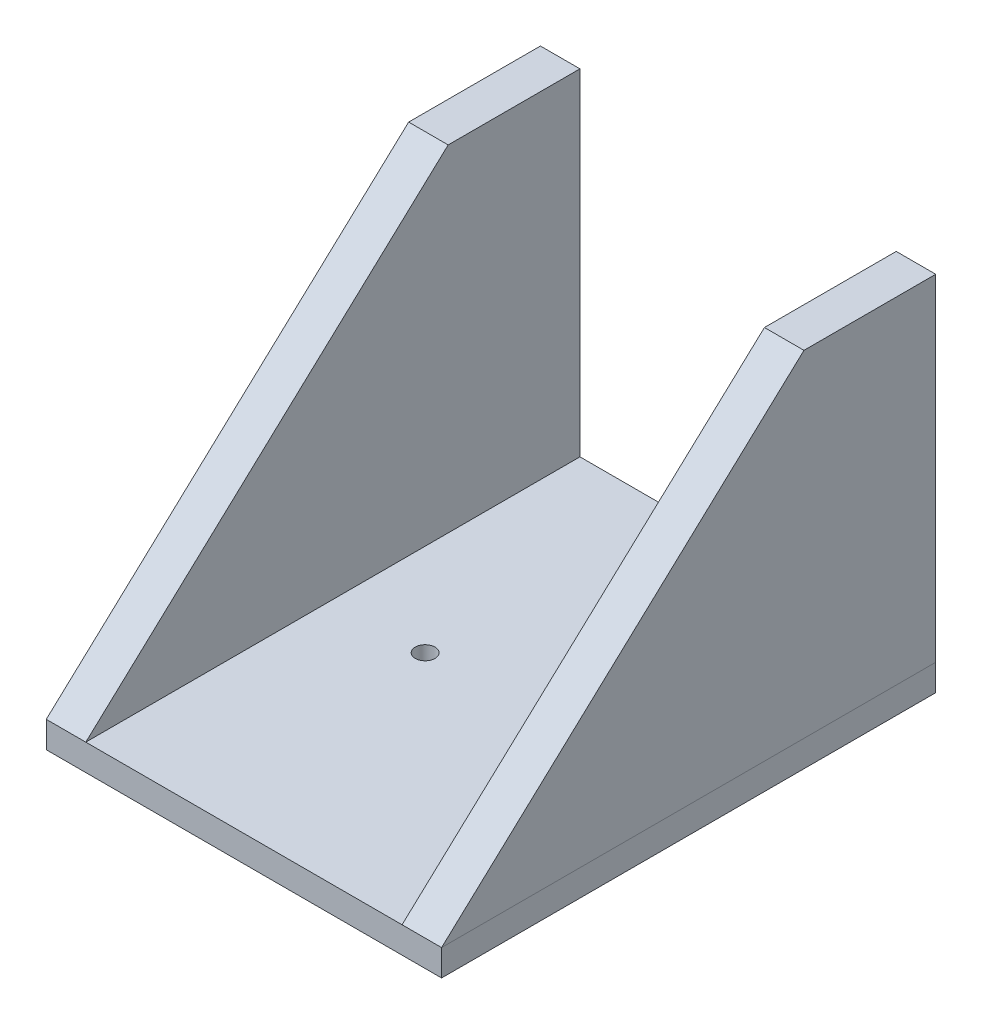
SolidWorks part; units mm, degrees
ref_plane "Front Plane" through (0, 0, 0) normal (0, 0, 1) x (1, 0, 0)
ref_plane "Top Plane" through (0, 0, 0) normal (0, 1, 0) x (1, 0, 0)
ref_plane "Right Plane" through (0, 0, 0) normal (1, 0, 0) x (0, 0, -1)
sketch "Sketch1" plane through (0, 0, 0) normal (0, 1, 0) x (1, 0, 0)
  line L0 (30, 0) -> (-30, 0)
  line L1 (-30, 0) -> (-30, 75)
  line L2 (-30, 75) -> (30, 75)
  line L3 (0, 0) -> (0, 87.606) construction
  line L4 (30, 0) -> (30, 75)
  point P5 (0, 0)
  point P9 (0, 75)
extrude "Boss-Extrude1" add sketch "Sketch1" along normal blind 4
sketch "Sketch2" plane through (0, 4, 0) normal (0, 1, 0) x (1, 0, 0)
  line L0 (-30, 37.5) -> (30, 37.5)
  line L1 (-30, 75) -> (-30, 0) construction
  line L2 (30, 0) -> (30, 75) construction
  line L3 (0, 37.5) -> (10, 37.5)
  line L4 (10, 37.5) -> (-10, 37.5)
  circle A0 centre (-10, 37.5) radius 1.5
  circle A1 centre (10, 37.5) radius 1.5
extrude "Cut-Extrude1" cut sketch "Sketch2" against normal blind 4 and the other way through all contours A0 | A1
sketch "Sketch3" plane through (0, 4, 0) normal (0, 1, 0) x (1, 0, 0)
  line L0 (-30, 75) -> (-24, 75)
  line L1 (30, 75) -> (-30, 75) construction
  line L2 (30, 75) -> (24, 75)
  line L3 (-24, 75) -> (-24, 0)
  line L4 (-30, 0) -> (30, 0) construction
  line L5 (-24, 0) -> (-30, 0)
  line L6 (-30, 0) -> (-30, 75)
  line L7 (24, 75) -> (24, 0)
  line L8 (24, 0) -> (30, 0)
  line L9 (30, 0) -> (30, 75)
  line L10 (-30, 75) -> (-24, 75)
  line L11 (-24, 75) -> (-24, 0)
  line L12 (-24, 0) -> (-30, 0)
  line L13 (-30, 0) -> (-30, 75)
  line L14 (30, 0) -> (30, 75)
  line L15 (-30, 75) -> (-24, 75)
  line L16 (-24, 75) -> (-24, 0)
  line L17 (-24, 0) -> (-30, 0)
  line L18 (-30, 0) -> (-30, 75)
  line L19 (30, 0) -> (30, 75)
  dimension "D1" = 6
  dimension "D2" = 6
ref_plane "Plane1" through (0, 55, 0) normal (0, 1, 0) x (1, 0, 0)
sketch "Sketch4" plane through (0, 55, 0) normal (0, 1, 0) x (1, 0, 0)
  line L0 (-30, 75) -> (-30, 55)
  line L1 (-30, 0) -> (-30, 75) construction
  line L2 (-30, 55) -> (-24, 55)
  line L3 (-24, 75) -> (-24, 0) construction
  line L4 (-24, 55) -> (-24, 75)
  line L5 (-24, 75) -> (-30, 75)
  line L6 (24, 75) -> (24, 55)
  line L7 (24, 75) -> (24, 0) construction
  line L8 (24, 55) -> (30, 55)
  line L9 (30, 0) -> (30, 75) construction
  line L10 (30, 55) -> (30, 75)
  line L11 (30, 75) -> (24, 75)
loft "Loft2" add section "Sketch3" section "Sketch4" connector at (24, 4, 0) connector at (24, 55, -55)
loft "Loft3" add section "Sketch3<11>" section "Sketch4<9>" connector at (-30, 4, 0) connector at (-30, 55, -55)
sketch "Sketch3<11>" plane through (0, 4, 0) normal (0, 1, 0) x (1, 0, 0) same geometry as "Sketch3"
sketch "Sketch4<9>" plane through (0, 55, 0) normal (0, 1, 0) x (1, 0, 0) same geometry as "Sketch4"
